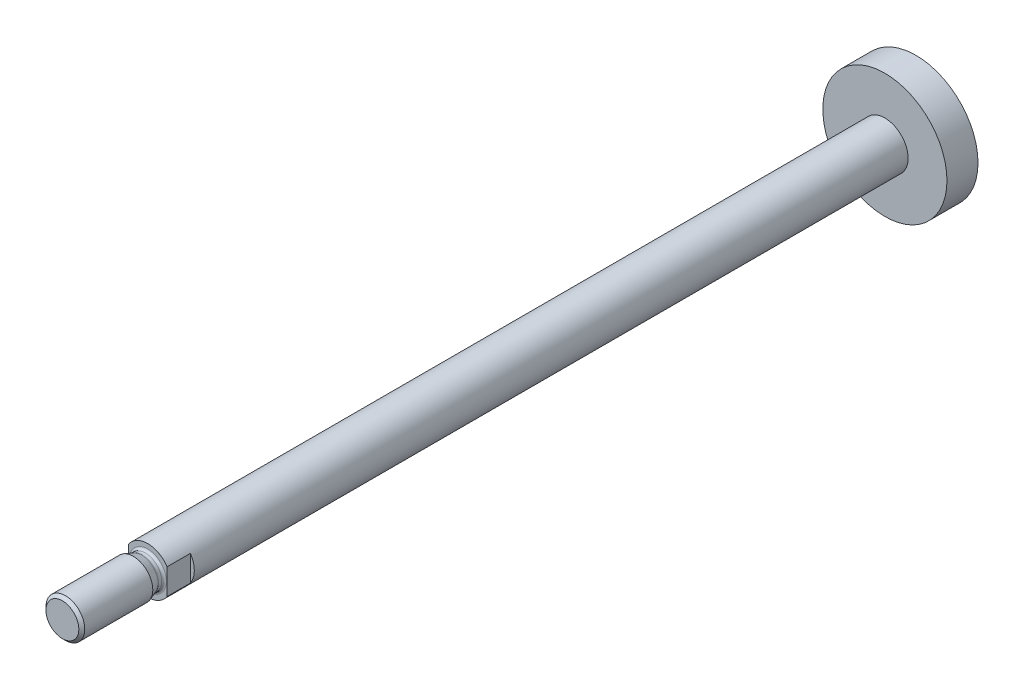
SolidWorks part; units mm, degrees
ref_plane "Ebene vorne" through (0, 0, 0) normal (0, 0, 1) x (1, 0, 0)
ref_plane "Ebene oben" through (0, 0, 0) normal (0, 1, 0) x (1, 0, 0)
ref_plane "Ebene rechts" through (0, 0, 0) normal (1, 0, 0) x (0, 0, -1)
sketch "Skizze1" plane through (0, 0, 0) normal (1, 0, 0) x (0, 0, -1)
  line L0 (-8, 0) -> (-8, 6)
  line L1 (-8, 6) -> (182, 6)
  line L2 (182, 6) -> (182, 16)
  line L3 (182, 16) -> (190, 16)
  line L4 (190, 16) -> (190, 0)
  line L5 (190, 0) -> (-8, 0)
  line L6 (190, 0) -> (-8, 0) construction
revolve "Rotation1" add sketch "Skizze1" angle 360 about L6 reverse direction yes
sketch "Skizze2" plane through (0, 0, 0) normal (1, 0, 0) x (0, 0, -1)
  line L0 (-30, 0) -> (-30, 4.233)
  line L1 (-30, 4.233) -> (-29.233, 5)
  line L2 (-29.233, 5) -> (-11.698, 5)
  line L3 (-11.698, 5) -> (-9.5994, 4.2362)
  line L4 (-9.3942, 4.2) -> (-8.6, 4.2)
  line L5 (-8, 4.8) -> (-8, 5)
  line L6 (-8, 5) -> (-7, 5)
  line L7 (-7, 5) -> (-7, 0)
  line L8 (-7, 0) -> (-30, 0)
  line L9 (-7, 0) -> (-30, 0) construction
  arc A0 (-9.5994, 4.2362) -> (-9.3942, 4.2) centre (-9.3942, 4.8) ccw
  arc A1 (-8.6, 4.2) -> (-8, 4.8) centre (-8.6, 4.8) ccw
revolve "Rotation2" add sketch "Skizze2" angle 360 about L9 reverse direction yes
cosmetic thread "Gewindedarstellung1" parameters "D1"=18.302, "D2"=8.466
ref_plane "Ebene1" through (0, 0, 8) normal (0, 0, 1) x (1, 0, 0)
ref_plane "Ebene2" through (0, 0, 2) normal (0, 0, 1) x (1, 0, 0)
sketch "Skizze3" plane through (0, 0, 2) normal (0, 0, 1) x (1, 0, 0)
  line L0 (-10, 20) -> (-10, -10)
  line L1 (-10, -10) -> (-5, -10)
  line L2 (-5, -10) -> (-5, 10)
  line L3 (-5, 10) -> (5, 10)
  line L4 (5, 10) -> (5, -10)
  line L5 (5, -10) -> (10, -10)
  line L6 (10, -10) -> (10, 20)
  line L7 (10, 20) -> (-10, 20)
extrude "Schnitt-Linear austragen1" cut sketch "Skizze3" along normal blind 7
ref_plane "Ebene3" through (0, 0, -379.5) normal (0, 0, 1) x (1, 0, 0)
ref_plane "Ebene4" through (0, 0, 22) normal (0, 0, 1) x (1, 0, 0)
ref_plane "Ebene5" through (0, 0, 17) normal (0, 0, 1) x (1, 0, 0)
ref_plane "FDT_KSAUFSATZ XY" through (0, 0, 17) normal (0, 0, 1) x (1, 0, 0)
ref_plane "FDT_KSAUFSATZ XZ" through (0, 0, 0) normal (0, 1, 0) x (1, 0, 0)
ref_plane "FDT_KSAUFSATZ YZ" through (0, 0, 0) normal (-1, 0, 0) x (0, 0, 1)
ref_axis "FDT_KSAUFSATZ X" through (80.9, 0, 17) along (-1, 0, 0)
ref_axis "FDT_KSAUFSATZ Y" through (0, 50, 17) along (0, -1, 0)
ref_axis "FDT_KSAUFSATZ Z" through (0, 0, 80.9) along (0, 0, -1)
sketch3d "FDT_KSAUFSATZ"
  point P0 (0, 0, 17)
ref_plane "FDT_NUT XY" through (0, 0, 17) normal (0, 0, 1) x (1, 0, 0)
ref_plane "FDT_NUT XZ" through (0, 0, 0) normal (0, 1, 0) x (1, 0, 0)
ref_plane "FDT_NUT YZ" through (0, 0, 0) normal (-1, 0, 0) x (0, 0, 1)
ref_axis "FDT_NUT X" through (80.9, 0, 17) along (-1, 0, 0)
ref_axis "FDT_NUT Y" through (0, 50, 17) along (0, -1, 0)
ref_axis "FDT_NUT Z" through (0, 0, 80.9) along (0, 0, -1)
sketch3d "FDT_NUT"
  point P0 (0, 0, 17)
ref_plane "KS XY" through (0, 0, 0) normal (0, 0, -1) x (-1, 0, 0)
ref_plane "KS XZ" through (0, 0, 0) normal (0, 1, 0) x (1, 0, 0)
ref_plane "KS YZ" through (0, 0, 0) normal (1, 0, 0) x (0, 0, -1)
ref_axis "KS X" through (-80.9, 0, 0) along (1, 0, 0)
ref_axis "KS Y" through (0, 50, 0) along (0, -1, 0)
ref_axis "KS Z" through (0, 0, -80.9) along (0, 0, 1)
sketch3d "KS"
  point P0 (0, 0, 0)
ref_plane "NUT1 XY" through (0, 0, 22) normal (0, 0, 1) x (1, 0, 0)
ref_plane "NUT1 XZ" through (0, 0, 0) normal (0, -1, 0) x (-1, 0, 0)
ref_plane "NUT1 YZ" through (0, 0, 0) normal (1, 0, 0) x (0, 0, -1)
ref_axis "NUT1 X" through (-80.9, 0, 22) along (1, 0, 0)
ref_axis "NUT1 Y" through (0, -50, 22) along (0, 1, 0)
ref_axis "NUT1 Z" through (0, 0, 80.9) along (0, 0, -1)
sketch3d "NUT1"
  point P0 (0, 0, 22)
